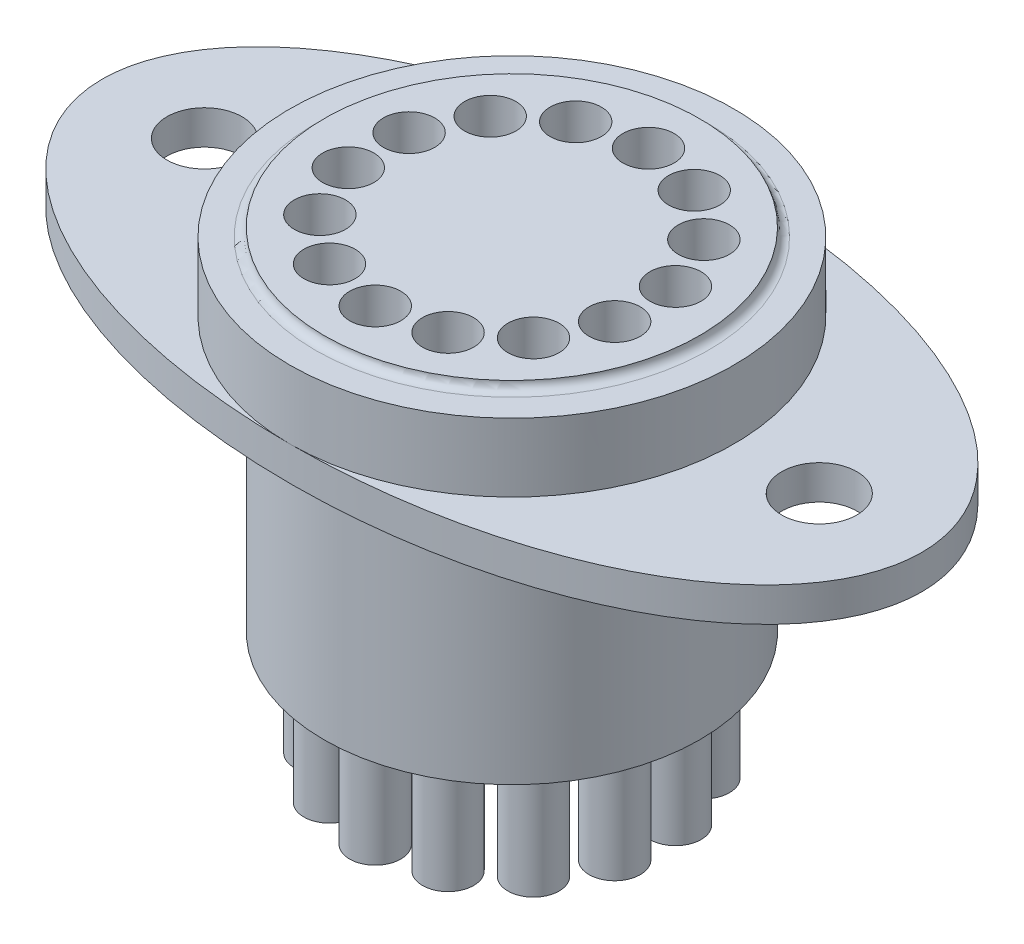
SolidWorks part; units mm, degrees
ref_plane "Front Plane" through (0, 0, 0) normal (0, 0, 1) x (1, 0, 0)
ref_plane "Top Plane" through (0, 0, 0) normal (0, 1, 0) x (1, 0, 0)
ref_plane "Right Plane" through (0, 0, 0) normal (1, 0, 0) x (0, 0, -1)
sketch "Sketch1" plane through (0, 0, 0) normal (0, 1, 0) x (1, 0, 0)
  circle A0 centre (0, 0) radius 6.5
  circle A1 centre (-9, 0) radius 1.1
  circle A2 centre (9, 0) radius 1.1
  ellipse E0 centre (0, 0) end of major axis (-12, 0) minor radius 6.5
  dimension "D1" = 13
  dimension "D2" = 2.2
  dimension "D3" = 2.2
  dimension "D4" = 18
  dimension "D5" = 9
  dimension "D6" = 0
  dimension "D7" = 24
extrude "Boss-Extrude1" add sketch "Sketch1" along normal blind 1
sketch "Sketch2" plane through (0, 1, 0) normal (0, 1, 0) x (1, 0, 0)
  circle A0 centre (0, 0) radius 6.5
  dimension "D1" = 13
extrude "Boss-Extrude2" add sketch "Sketch2" along normal blind 2
sketch "Sketch4" plane through (0, 0, 0) normal (0, -1, 0) x (1, 0, 0)
  circle A0 centre (0, 0) radius 5.5
  dimension "D1" = 11
extrude "Boss-Extrude3" add sketch "Sketch4" along normal blind 7
sketch "Sketch7" plane through (0, 3, 0) normal (0, 1, 0) x (1, 0, 0)
  circle A0 centre (0, 0) radius 5.5
  dimension "D1" = 11
extrude "Boss-Extrude5" add sketch "Sketch7" along normal blind 0.25
sketch "Sketch5" plane through (0, 3.25, 0) normal (0, 1, 0) x (1, 0, 0)
  circle A0 centre (0, -4) radius 0.75
  circle A1 centre (-1.7355, -3.6039) radius 0.75
  circle A2 centre (-3.1273, -2.494) radius 0.75
  circle A3 centre (-3.8997, -0.8901) radius 0.75
  circle A4 centre (-3.8997, 0.8901) radius 0.75
  circle A5 centre (-3.1273, 2.494) radius 0.75
  circle A6 centre (-1.7355, 3.6039) radius 0.75
  circle A7 centre (0, 4) radius 0.75
  circle A8 centre (1.7355, 3.6039) radius 0.75
  circle A9 centre (3.1273, 2.494) radius 0.75
  circle A10 centre (3.8997, 0.8901) radius 0.75
  circle A11 centre (3.8997, -0.8901) radius 0.75
  circle A12 centre (3.1273, -2.494) radius 0.75
  circle A13 centre (1.7355, -3.6039) radius 0.75
  point P32 (0, 0)
  dimension "D2" = 1.5
  dimension "D1" = 4
  dimension "D3" = 14
extrude "Cut-Extrude2" cut sketch "Sketch5" against normal blind 7
sketch "Sketch6" plane through (0, -7, 0) normal (0, -1, 0) x (1, 0, 0)
  circle A0 centre (0, -4) radius 0.75
  circle A1 centre (-1.7355, -3.6039) radius 0.75
  circle A2 centre (-3.1273, -2.494) radius 0.75
  circle A3 centre (-3.8997, -0.8901) radius 0.75
  circle A4 centre (-3.8997, 0.8901) radius 0.75
  circle A5 centre (-3.1273, 2.494) radius 0.75
  circle A6 centre (-1.7355, 3.6039) radius 0.75
  circle A7 centre (0, 4) radius 0.75
  circle A8 centre (1.7355, 3.6039) radius 0.75
  circle A9 centre (3.1273, 2.494) radius 0.75
  circle A10 centre (3.8997, 0.8901) radius 0.75
  circle A11 centre (3.8997, -0.8901) radius 0.75
  circle A12 centre (3.1273, -2.494) radius 0.75
  circle A13 centre (1.7355, -3.6039) radius 0.75
  point P32 (0, 0)
  dimension "D1" = 1.5
  dimension "D2" = 4
  dimension "D3" = 14
extrude "Boss-Extrude4" add sketch "Sketch6" along normal blind 3.4
fillet "Fillet1" radius 0.25 1 edges at (0, 3, 5.5)
